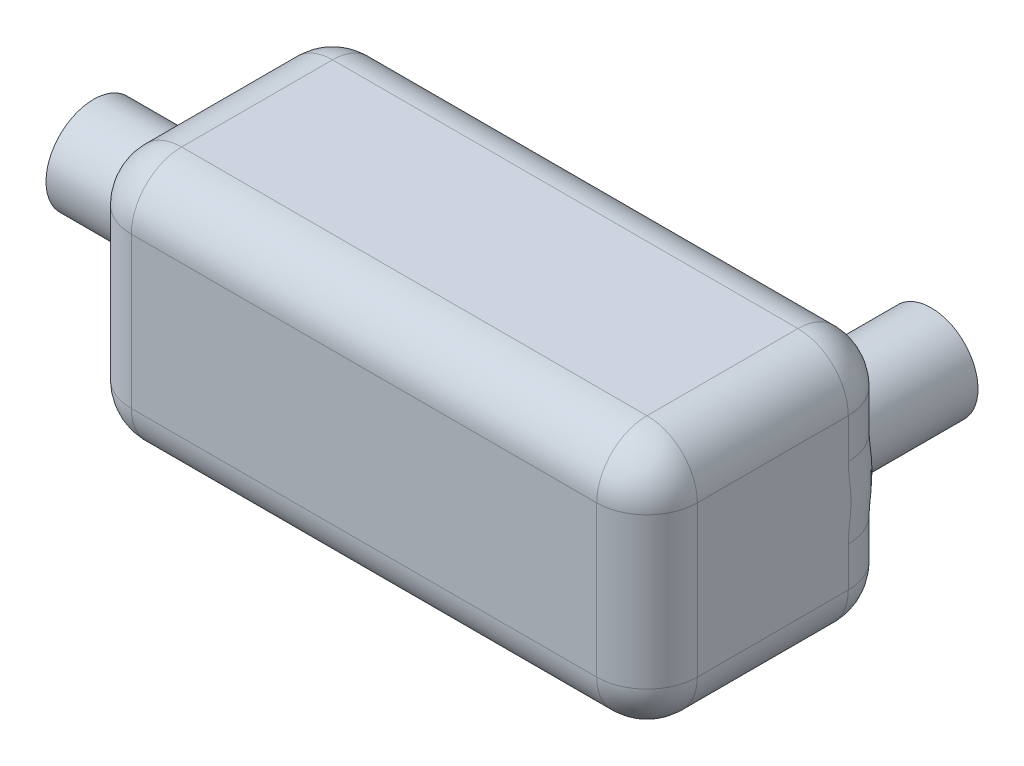
SolidWorks part; units mm, degrees
ref_plane "Alzado" through (0, 0, 0) normal (0, 0, 1) x (1, 0, 0)
ref_plane "Planta" through (0, 0, 0) normal (0, 1, 0) x (1, 0, 0)
ref_plane "Vista lateral" through (0, 0, 0) normal (1, 0, 0) x (0, 0, -1)
sketch "Croquis1" plane through (0, 0, 0) normal (0, 1, 0) x (1, 0, 0)
  line L1 (-45, 20) -> (45, 20)
  line L2 (-45, 20) -> (-45, -20)
  line L3 (-45, -20) -> (45, -20)
  line L4 (45, 20) -> (45, -20)
  line L5 (-45, 20) -> (45, -20) construction
  line L6 (-45, -20) -> (45, 20) construction
  point P0 (0, 0)
  dimension "D1" = 40
  dimension "D2" = 90
extrude "Saliente-Extruir1" add sketch "Croquis1" along normal blind 40
sketch "Croquis2" plane through (0, 0, -20) normal (0, 0, -1) x (-1, 0, 0)
  line L0 (-45, 20) -> (-32.1793, 20) construction
  line L1 (-45, 40) -> (-45, 0) construction
  line L2 (-32.1793, 20) -> (-32.1793, 40) construction
  line L3 (-45, 40) -> (45, 40) construction
  circle A0 centre (-32.1793, 20) radius 7.4473
  circle A1 centre (-32.1793, 20) radius 6.35
  dimension "D1" = 12.7
extrude "Saliente-Extruir2" add sketch "Croquis2" along normal blind 18
sketch "Croquis3" plane through (-45, 0, 0) normal (-1, 0, 0) x (0, 0, 1)
  line L0 (0, 40) -> (0, 0) construction
  line L1 (-20, 40) -> (20, 40) construction
  line L2 (0, 0) -> (0, 20) construction
  line L3 (0, 20) -> (20, 20) construction
  line L4 (20, 40) -> (20, 0) construction
  circle A0 centre (0, 20) radius 6.35
  circle A1 centre (0, 20) radius 7.5599
  dimension "D1" = 12.7
extrude "Saliente-Extruir3" add sketch "Croquis3" along normal blind 18
fillet "Redondeo1" radius 8 4 edges at (45, 20, 20) (45, 20, -20) (-45, 20, 20) (-45, 20, -20)
fillet "Redondeo2" radius 8 16 edges at (-42.6569, 0, 17.6569) (-45, 0, 0) (-42.6569, 0, -17.6569) (42.6569, 0, -17.6569) (45, 0, 0) (42.6569, 0, 17.6569) (-42.6569, 40, 17.6569) (-45, 40, 0) (-42.6569, 40, -17.6569) (42.6569, 40, -17.6569) (45, 40, 0) (42.6569, 40, 17.6569) (0, 40, -20) (0, 0, -20) (0, 0, 20) (0, 40, 20)
